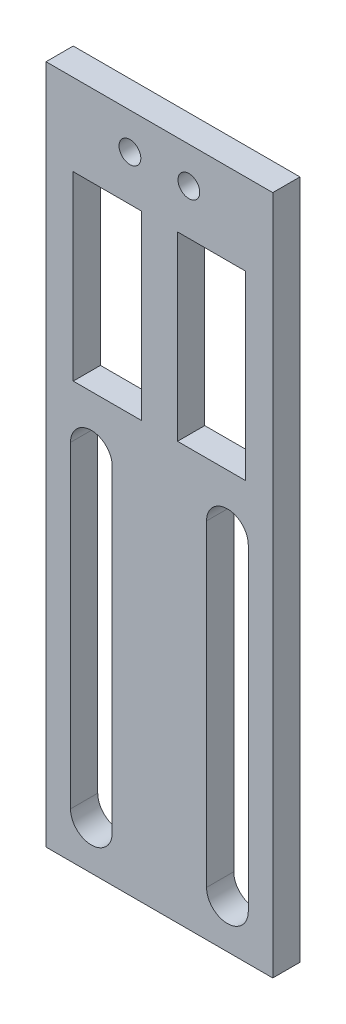
SolidWorks part; units mm, degrees
material "ABS"
ref_plane "Front Plane" through (0, 0, 0) normal (0, 0, 1) x (1, 0, 0)
ref_plane "Top Plane" through (0, 0, 0) normal (0, 1, 0) x (1, 0, 0)
ref_plane "Right Plane" through (0, 0, 0) normal (1, 0, 0) x (0, 0, -1)
sketch "Sketch1" plane through (0, 0, 0) normal (0, 0, 1) x (1, 0, 0)
  line L1 (12.5, 37.5) -> (-12.5, 37.5)
  line L2 (12.5, 37.5) -> (12.5, -37.5)
  line L3 (12.5, -37.5) -> (-12.5, -37.5)
  line L4 (-12.5, 37.5) -> (-12.5, -37.5)
  line L5 (12.5, 37.5) -> (-12.5, -37.5) construction
  line L6 (12.5, -37.5) -> (-12.5, 37.5) construction
  point P0 (0, 0)
  dimension "D1" = 25
  dimension "D2" = 75
extrude "Boss-Extrude1" add sketch "Sketch1" along normal blind 3
sketch "Sketch2" plane through (0, 0, 3) normal (0, 0, 1) x (1, 0, 0)
  line L0 (-7.5, -32.5) -> (-7.5, 2.5) construction
  line L1 (-9.5, 28.5) -> (-2, 28.5)
  line L2 (-9.5, 28.5) -> (-9.5, 8.5)
  line L3 (-9.5, 8.5) -> (-2, 8.5)
  line L4 (-2, 28.5) -> (-2, 8.5)
  line L5 (2, 28.5) -> (9.5, 28.5)
  line L6 (2, 28.5) -> (2, 8.5)
  line L7 (2, 8.5) -> (9.5, 8.5)
  line L8 (9.5, 28.5) -> (9.5, 8.5)
  line L9 (-9.8, -32.5) -> (-9.8, 2.5)
  line L10 (-5.2, -32.5) -> (-5.2, 2.5)
  line L11 (7.5, -32.5) -> (7.5, 2.5) construction
  line L12 (5.2, -32.5) -> (5.2, 2.5)
  line L13 (9.8, -32.5) -> (9.8, 2.5)
  line L14 (12.5, 37.5) -> (-12.5, 37.5) construction
  line L15 (-2, 28.5) -> (2, 28.5) construction
  line L16 (0, 28.5) -> (0, 37.5) construction
  line L17 (12.5, -37.5) -> (12.5, 37.5) construction
  line L18 (-12.5, 37.5) -> (-12.5, -37.5) construction
  line L19 (-12.5, -37.5) -> (12.5, -37.5) construction
  line L20 (-3.25, 33.5) -> (3.25, 33.5) construction
  line L21 (0, 33.5) -> (0, 37.5) construction
  arc A0 (-9.8, -32.5) -> (-5.2, -32.5) centre (-7.5, -32.5) ccw
  arc A1 (-5.2, 2.5) -> (-9.8, 2.5) centre (-7.5, 2.5) ccw
  arc A2 (5.2, -32.5) -> (9.8, -32.5) centre (7.5, -32.5) ccw
  arc A3 (9.8, 2.5) -> (5.2, 2.5) centre (7.5, 2.5) ccw
  circle A4 centre (-3.25, 33.5) radius 1.2
  circle A5 centre (3.25, 33.5) radius 1.2
  point P10 (-7.5, -15)
  point P16 (7.5, -15)
  dimension "D8" = 5
  dimension "D10" = 2.4
  dimension "D12" = 4
  dimension "D1" = 7.5
  dimension "D2" = 20
  dimension "D3" = 9
  dimension "D4" = 4
  dimension "D5" = 4.6
  dimension "D6" = 2.7
  dimension "D7" = 2.7
  dimension "D9" = 35
  dimension "D11" = 6.5
extrude "Cut-Extrude1" cut sketch "Sketch2" against normal through all
